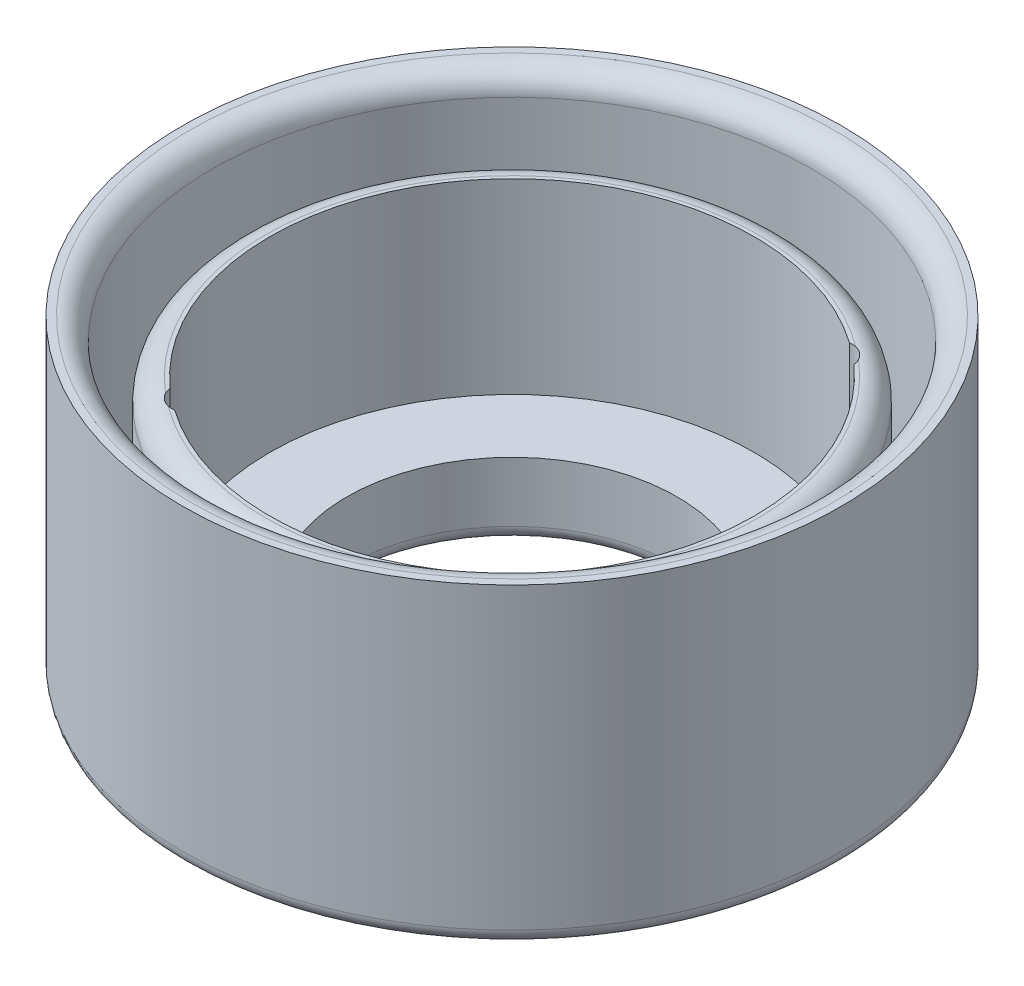
SolidWorks part; units mm, degrees
ref_plane "Alzado" through (0, 0, 0) normal (0, 0, 1) x (1, 0, 0)
ref_plane "Planta" through (0, 0, 0) normal (0, 1, 0) x (1, 0, 0)
ref_plane "Vista lateral" through (0, 0, 0) normal (1, 0, 0) x (0, 0, -1)
sketch "Croquis1" plane through (0, 0, 0) normal (0, 1, 0) x (1, 0, 0)
  circle A0 centre (0, 0) radius 17.95
  circle A1 centre (0, 0) radius 20.05
  circle A2 centre (0, 0) radius 22.05
  circle A3 centre (0, 0) radius 16.2
  dimension "D1" = 35.9
  dimension "D2" = 1.75
  dimension "D3" = 40.1
  dimension "D4" = 2
extrude "Saliente-Extruir1" add sketch "Croquis1" along normal blind 16 contours A2 A1 region at (-21.4263, 0, 0)
extrude "Saliente-Extruir2" add sketch "Croquis1<4>" along normal blind 12.5 separate body contours A0 A3 region at (-17.4423, 0, 0)
sketch "Croquis1<4>" plane through (0, 0, 0) normal (0, 1, 0) x (1, 0, 0) same geometry as "Croquis1"
extrude "Saliente-Extruir4" add sketch "Croquis1<6>" against normal blind 5 contours A3 | A0 A3 | A1 A0 | A2 A1 region at (-17.4423, 0, 0) region at (-19.4829, 0, 0) region at (-21.4263, 0, 0) region at (0, 0, 0)
sketch "Croquis1<6>" plane through (0, 0, 0) normal (0, 1, 0) x (1, 0, 0) same geometry as "Croquis1"
sketch "Croquis4" plane through (0, -5, 0) normal (0, -1, 0) x (1, 0, 0)
  line L0 (-9.5, 12) -> (0, 0) construction
  line L1 (0, 0) -> (9.5, -12) construction
  circle A0 centre (0, 0) radius 11.05
  circle A1 centre (-9.5, 12) radius 1.25
  circle A2 centre (9.5, -12) radius 1.25
  dimension "D1" = 22.1
  dimension "D4" = 2.5
  dimension "D2" = 19
  dimension "D3" = 24
extrude "Cortar-Extruir1" cut sketch "Croquis4" against normal up to next
fillet "Redondeo1" radius 1 1 edges at (0, -5, -11.05)
fillet "Redondeo2" radius 1.5 2 edges at (0, 12.5, 17.95) (0, 16, 20.05)
fillet "Redondeo3" radius 1 1 edges at (0, -5, 22.05)
